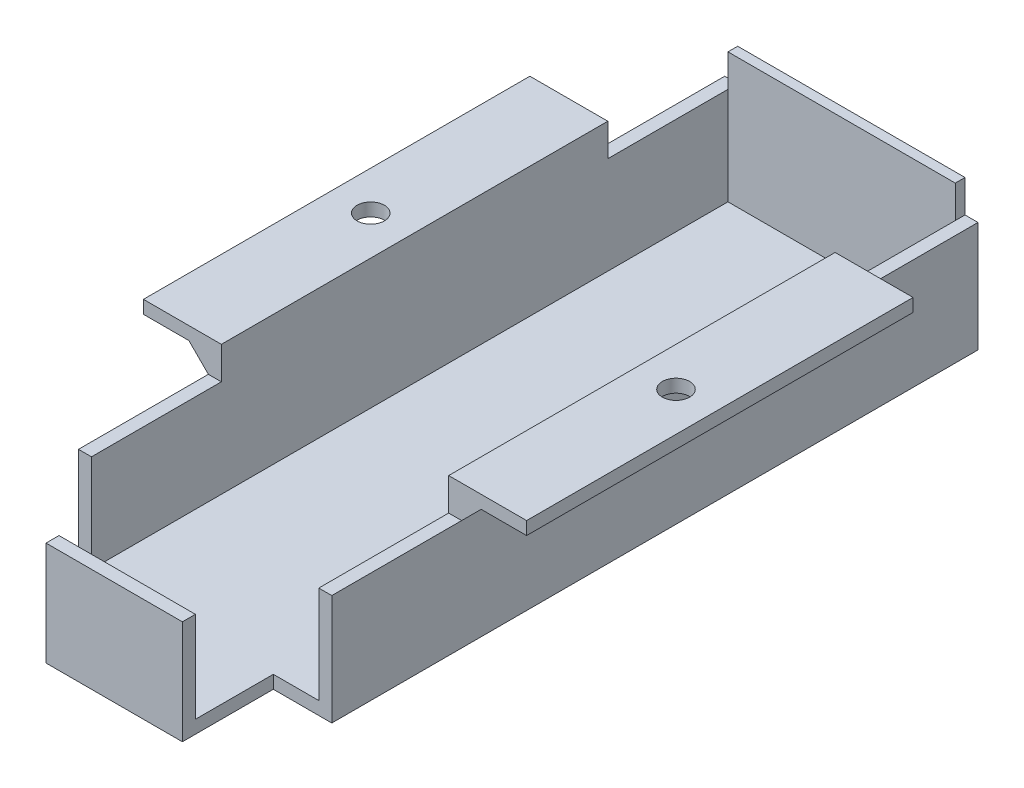
SolidWorks part; units mm, degrees
ref_plane "Front Plane" through (0, 0, 0) normal (0, 0, 1) x (1, 0, 0)
ref_plane "Top Plane" through (0, 0, 0) normal (0, 1, 0) x (1, 0, 0)
ref_plane "Right Plane" through (0, 0, 0) normal (1, 0, 0) x (0, 0, -1)
sketch "Sketch1" plane through (0, 0, 0) normal (0, 0, 1) x (1, 0, 0)
  line L0 (-29.5, 0) -> (-17.5, 0)
  line L1 (-17.5, 0) -> (-17.5, -20)
  line L2 (-17.5, -20) -> (17.5, -20)
  line L3 (0, -618.9467) -> (0, 30328.3864) construction
  line L5 (29.5, -2) -> (29.5, 0)
  line L6 (19.5, -2) -> (29.5, -2)
  line L7 (19.5, -22) -> (19.5, -2)
  line L8 (19.5, -22) -> (-19.5, -22)
  line L9 (-19.5, -22) -> (-19.5, -2)
  line L10 (-19.5, -2) -> (-29.5, -2)
  line L11 (-29.5, -2) -> (-29.5, 0)
  line L12 (17.5, 0) -> (17.5, -20)
  line L13 (29.5, 0) -> (17.5, 0)
  dimension "D1" = 35
  dimension "D2" = 20
  dimension "D3" = 2
  dimension "D4" = 2
  dimension "D5" = 2
  dimension "D6" = 10
extrude "Boss-Extrude1" add sketch "Sketch1" along normal mid plane 98
sketch "Sketch3" plane through (0, 0, 0) normal (1, 0, 0) x (0, 0, -1)
  line L0 (-49, -22) -> (-63, -22)
  line L1 (-63, -22) -> (-63, -6)
  line L2 (-63, -6) -> (-61, -6)
  line L3 (-61, -6) -> (-61, -20)
  line L4 (-61, -20) -> (-49, -20)
  line L5 (-49, -22) -> (-49, -2) construction
  line L6 (-49, -20) -> (-49, -22)
  line L8 (49, -20) -> (49, 0) construction
  dimension "D2" = 2
  dimension "D4" = 16
  dimension "D1" = 110
extrude "Boss-Extrude3" add sketch "Sketch3" along normal mid plane 21
chamfer "Chamfer1" distance 3 angle 45 2 edges at (19.5, -2, 0) (-19.5, -2, 0)
sketch "Sketch4" plane through (0, 0, 0) normal (0, 1, 0) x (1, 0, 0)
  line L0 (-23.5, 0) -> (23.5, 0) construction
  circle A0 centre (-23.5, 0) radius 2.1
  circle A1 centre (23.5, 0) radius 2.1
  point P4 (0, 0)
  dimension "D1" = 4.2
  dimension "D2" = 4.2
  dimension "D3" = 47
extrude "Cut-Extrude1" cut sketch "Sketch4" against normal through all
sketch "Sketch5" plane through (0, -2, 0) normal (0, -1, 0) x (1, 0, 0)
  line L0 (19.5, -49) -> (19.5, 49) construction
  line L1 (27.5, -5) -> (19.5, -5)
  line L2 (27.5, -5) -> (27.5, 5)
  line L3 (27.5, 5) -> (19.5, 5)
  line L4 (19.5, -5) -> (19.5, 5)
  line L5 (27.5, -5) -> (19.5, 5) construction
  line L6 (27.5, 5) -> (19.5, -5) construction
  line L7 (-19.5, 49) -> (-19.5, -49) construction
  line L8 (-27.5, -5) -> (-19.5, -5)
  line L9 (-27.5, -5) -> (-27.5, 5)
  line L10 (-27.5, 5) -> (-19.5, 5)
  line L11 (-19.5, -5) -> (-19.5, 5)
  line L12 (-27.5, -5) -> (-19.5, 5) construction
  line L13 (-27.5, 5) -> (-19.5, -5) construction
  point P0 (23.5, 0)
  point P8 (-23.5, 0)
  dimension "D1" = 10
extrude "Cut-Extrude2" cut sketch "Sketch5" along normal through all
sketch "Sketch2" plane through (0, 0, -49) normal (0, 0, -1) x (-1, 0, 0)
  line L0 (-17.5, 0) -> (17.5, 0)
  line L18 (29.5, -2) -> (29.5, 0)
  line L19 (29.5, 0) -> (17.5, 0)
  line L20 (17.5, 0) -> (17.5, -20)
  line L21 (17.5, -20) -> (-17.5, -20)
  line L22 (-17.5, -20) -> (-17.5, 0)
  line L23 (-17.5, 0) -> (-29.5, 0)
  line L24 (-29.5, 0) -> (-29.5, -2)
  line L25 (-29.5, -2) -> (-22.5, -2)
  line L26 (-22.5, -2) -> (-19.5, -5)
  line L27 (-19.5, -5) -> (-19.5, -22)
  line L28 (-19.5, -22) -> (19.5, -22)
  line L29 (19.5, -22) -> (19.5, -5)
  line L30 (19.5, -5) -> (22.5, -2)
  line L31 (22.5, -2) -> (29.5, -2)
  line L32 (29.5, -2) -> (29.5, 0)
  line L33 (29.5, 0) -> (17.5, 0)
  line L37 (-17.5, 0) -> (-29.5, 0)
  line L38 (-29.5, 0) -> (-29.5, -2)
  line L39 (-29.5, -2) -> (-22.5, -2)
  line L40 (-22.5, -2) -> (-19.5, -5)
  line L41 (-19.5, -5) -> (-19.5, -22)
  line L42 (-19.5, -22) -> (19.5, -22)
  line L43 (19.5, -22) -> (19.5, -5)
  line L44 (19.5, -5) -> (22.5, -2)
  line L45 (22.5, -2) -> (29.5, -2)
  dimension "D1" = 0
extrude "Boss-Extrude5" add sketch "Sketch2" along normal blind 1.5
sketch "Sketch6" plane through (0, 0, 0) normal (0, 1, 0) x (1, 0, 0)
  line L0 (-17.5, -49) -> (-17.5, 49) construction
  line L1 (-29.5, -49) -> (-17.5, -49)
  line L2 (-29.5, -49) -> (-29.5, -29)
  line L3 (-29.5, -29) -> (-17.5, -29)
  line L4 (-17.5, -49) -> (-17.5, -29)
  line L5 (17.5, -49) -> (17.5, 49) construction
  line L6 (29.5, -49) -> (17.5, -49)
  line L7 (29.5, -49) -> (29.5, -29)
  line L8 (29.5, -29) -> (17.5, -29)
  line L9 (17.5, -49) -> (17.5, -29)
  line L11 (29.5, 50.5) -> (17.5, 50.5)
  line L12 (29.5, 50.5) -> (29.5, 30.5)
  line L13 (29.5, 30.5) -> (17.5, 30.5)
  line L14 (17.5, 50.5) -> (17.5, 30.5)
  line L15 (-29.5, 50.5) -> (-17.5, 50.5)
  line L16 (-29.5, 50.5) -> (-29.5, 30.5)
  line L17 (-29.5, 30.5) -> (-17.5, 30.5)
  line L18 (-17.5, 50.5) -> (-17.5, 30.5)
  dimension "D1" = 20
extrude "Cut-Extrude3" cut sketch "Sketch6" against normal up to vertex (5 mm away) up to point (-19.5, -5, 5)
equation "\"D4@Sketch1\"=\"D3@Sketch1\""
equation "\"D5@Sketch1\"=\"D3@Sketch1\""
equation "\"D2@Sketch3\"=\"D3@Sketch3\""
equation "\"width\"= 24"
equation "\"thk\"= 3"
equation "\"holesize\"= 4.2"
equation "\"holedistance\"= ( 20 + 12 ) / 2"
equation "\"threaded_hole\"= 3.9"
equation "\"fillet_radius\"= 2"
equation "\"ground_clearance\"= 25"
equation "\"tire_thk\"= 3"
equation "\"innerwheel_diam\" = \"wheel_diam\"-2*\"tire_thk\""
equation "\"innerwheel_thk\"= 8"
equation "\"wheel_diam\"= 2*(\"width\"/2+\"ground_clearance\")"
equation "\"coloursensor_holesize\"= 2.65"
equation "\"hole_to_edge\" = 4"
equation "\"D1@Sketch4\"=\"holesize\""
equation "\"D2@Sketch4\"=\"D1@Sketch4\""
